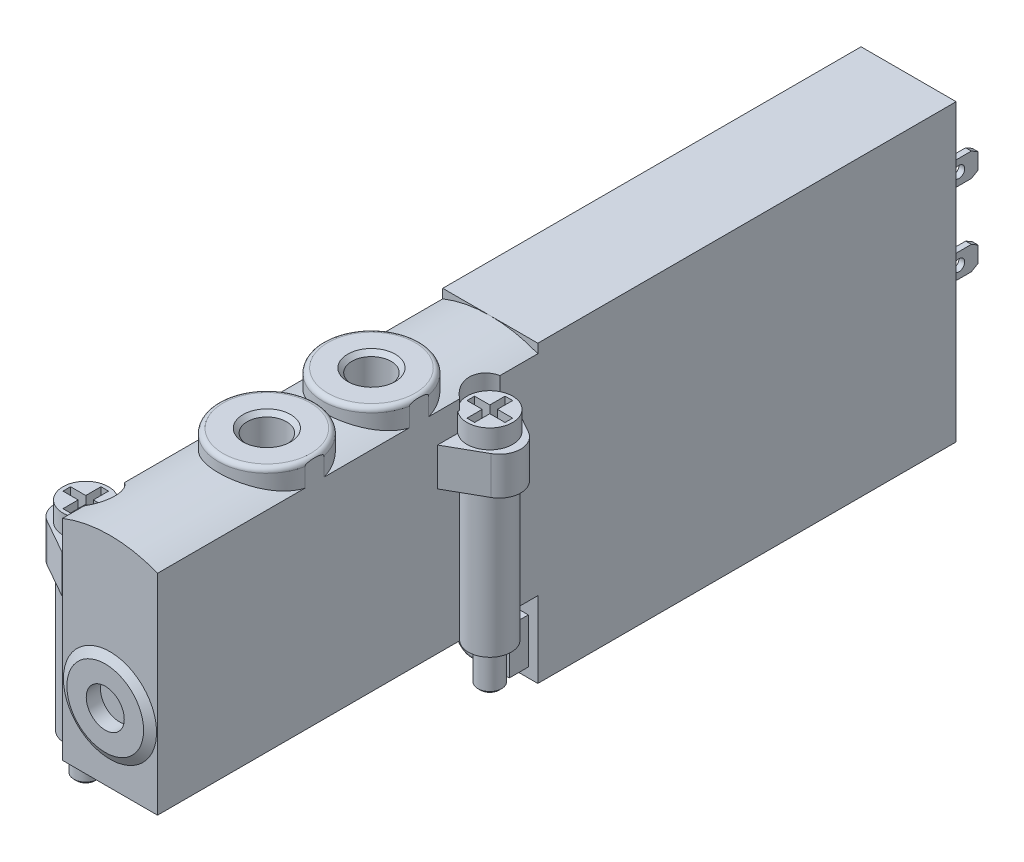
SolidWorks part; units mm, degrees
ref_plane "Front Plane" through (0, 0, 0) normal (0, 0, 1) x (1, 0, 0)
ref_plane "Top Plane" through (0, 0, 0) normal (0, 1, 0) x (1, 0, 0)
ref_plane "Right Plane" through (0, 0, 0) normal (1, 0, 0) x (0, 0, -1)
sketch "Sketch1" plane through (0, 0, 0) normal (1, 0, 0) x (0, 0, -1)
  line L0 (-42, 31) -> (-42, 8)
  line L1 (-42, 8) -> (-2, 8)
  line L2 (-2, 8) -> (-2, 0)
  line L3 (-2, 0) -> (42, 0)
  line L4 (42, 0) -> (42, 31)
  line L5 (42, 31) -> (-42, 31)
extrude "Boss-Extrude1" add sketch "Sketch1" against normal blind 5 and the other way blind 5
sketch "Sketch2" plane through (0, 0, 0) normal (1, 0, 0) x (0, 0, -1)
  line L0 (42, 15.5) -> (42, 17.5)
  line L1 (42, 17.5) -> (44.3, 17.5)
  line L2 (44.3, 17.5) -> (44.5, 17.3)
  line L3 (44.5, 17.3) -> (44.5, 15.5)
  line L4 (44.5, 15.5) -> (42, 15.5)
  line L5 (44.5, 15.5) -> (42, 15.5) construction
revolve "Revolve1" add sketch "Sketch2" angle 360 about L5 reverse direction yes
sketch "Sketch3" plane through (0, 0, 0) normal (1, 0, 0) x (0, 0, -1)
  line L0 (42, 18) -> (42.5, 18.5)
  line L1 (42.5, 18.5) -> (48.3, 18.5)
  line L2 (48.3, 18.5) -> (49, 18.9041)
  line L3 (49, 18.9041) -> (49, 20.5959)
  line L4 (49, 20.5959) -> (48.3, 21)
  line L5 (48.3, 21) -> (42.5, 21)
  line L6 (42.5, 21) -> (42, 21.5)
  line L7 (42, 21.5) -> (42, 18)
  circle A0 centre (47, 19.75) radius 0.6
extrude "Boss-Extrude2" add sketch "Sketch3" against normal blind 0.3 and the other way blind 0.3
sketch "Sketch4" plane through (0, 0, 0) normal (1, 0, 0) x (0, 0, -1)
  line L0 (42, 13) -> (42, 9.5)
  line L1 (42, 9.5) -> (42.5, 10)
  line L2 (42.5, 10) -> (48.3, 10)
  line L3 (48.3, 10) -> (49, 10.4041)
  line L4 (49, 10.4041) -> (49, 12.0959)
  line L5 (49, 12.0959) -> (48.3, 12.5)
  line L6 (48.3, 12.5) -> (42.5, 12.5)
  line L7 (42.5, 12.5) -> (42, 13)
  circle A0 centre (47, 11.25) radius 0.6
extrude "Boss-Extrude3" add sketch "Sketch4" against normal blind 0.3 and the other way blind 0.3
sketch "Sketch5" plane through (0, 0, 0) normal (1, 0, 0) x (0, 0, -1)
  line L0 (-42.5, 15.5) -> (-42.5, 19.534)
  line L1 (-42.5, 19.534) -> (-42, 20.4)
  line L2 (-42, 20.4) -> (-42, 15.5)
  line L3 (-42, 15.5) -> (-42.5, 15.5)
  line L4 (-42, 15.5) -> (-42.5, 15.5) construction
revolve "Revolve2" add sketch "Sketch5" angle 360 about L4 reverse direction yes
ref_plane "Plane1" through (0, 0, 42.5) normal (0, 0, 1) x (1, 0, 0)
sketch "Sketch6" plane through (0, 0, 42.5) normal (0, 0, 1) x (1, 0, 0)
  circle A0 centre (0, 15.5) radius 2
extrude "Cut-Extrude1" cut sketch "Sketch6" along normal blind 1.5 and the other way blind 1.5
ref_plane "Plane2" through (2, 0, 0) normal (1, 0, 0) x (0, 0, -1)
ref_plane "Plane3" through (0, 23, 0) normal (0, 1, 0) x (1, 0, 0)
sketch "Sketch7" plane through (0, 23, 0) normal (0, 1, 0) x (1, 0, 0)
  line L0 (5, -12.55) -> (8.6081, -10.5082)
  line L1 (8.6081, -6.5918) -> (5, -4.55)
  line L2 (5, -4.55) -> (5, -12.55)
  arc A0 (8.6081, -10.5082) -> (8.6081, -6.5918) centre (7.5, -8.55) ccw
extrude "Boss-Extrude4" add sketch "Sketch7" along normal blind 4
sketch "Sketch8" plane through (0, 23, 0) normal (0, 1, 0) x (1, 0, 0)
  line L0 (-8.6081, -40.0082) -> (-5, -42.05)
  line L1 (-5, -42.05) -> (-5, -34.05)
  line L2 (-5, -34.05) -> (-8.6081, -36.0918)
  arc A0 (-8.6081, -36.0918) -> (-8.6081, -40.0082) centre (-7.5, -38.05) ccw
extrude "Boss-Extrude5" add sketch "Sketch8" along normal blind 4
ref_plane "Plane4" through (0, 27, 0) normal (0, 1, 0) x (1, 0, 0)
sketch "Sketch9" plane through (0, 27, 0) normal (0, 1, 0) x (1, 0, 0)
  circle A0 centre (6.5, -8.1) radius 2.6
extrude "Cut-Extrude2" cut sketch "Sketch9" along normal blind 5
sketch "Sketch10" plane through (0, 27, 0) normal (0, 1, 0) x (1, 0, 0)
  circle A0 centre (-6.5, -37.6) radius 2.6
extrude "Cut-Extrude3" cut sketch "Sketch10" along normal blind 5
ref_plane "Plane5" through (6.5, 0, 0) normal (1, 0, 0) x (0, 0, -1)
sketch "Sketch11" plane through (6.5, 0, 0) normal (1, 0, 0) x (0, 0, -1)
  line L0 (-8.55, 29) -> (-6.15, 29)
  line L1 (-6.15, 29) -> (-6.15, 26.5)
  line L2 (-6.15, 26.5) -> (-6.3, 26.5)
  line L3 (-6.3, 26.5) -> (-6.3, 8)
  line L4 (-6.3, 8) -> (-7.3, 8)
  line L5 (-7.3, 8) -> (-7.3, 4.176)
  line L6 (-7.3, 4.176) -> (-7.576, 3.9)
  line L7 (-7.576, 3.9) -> (-8.55, 3.9)
  line L8 (-8.55, 3.9) -> (-8.55, 29)
  line L9 (-8.55, 3.9) -> (-8.55, 29) construction
revolve "Revolve3" add sketch "Sketch11" angle 360 about L9 reverse direction yes
cosmetic thread "Cosmetic Thread1" parameters "D1"=3.5, "D2"=1.948
ref_plane "Plane6" through (-6.5, 0, 0) normal (1, 0, 0) x (0, 0, -1)
sketch "Sketch12" plane through (-6.5, 0, 0) normal (1, 0, 0) x (0, 0, -1)
  line L0 (-38.05, 29) -> (-35.65, 29)
  line L1 (-35.65, 29) -> (-35.65, 26.5)
  line L2 (-35.65, 26.5) -> (-35.8, 26.5)
  line L3 (-35.8, 26.5) -> (-35.8, 8)
  line L4 (-35.8, 8) -> (-36.8, 8)
  line L5 (-36.8, 8) -> (-36.8, 4.176)
  line L6 (-36.8, 4.176) -> (-37.076, 3.9)
  line L7 (-37.076, 3.9) -> (-38.05, 3.9)
  line L8 (-38.05, 3.9) -> (-38.05, 29)
  line L9 (-38.05, 3.9) -> (-38.05, 29) construction
revolve "Revolve4" add sketch "Sketch12" angle 360 about L9 reverse direction yes
cosmetic thread "Cosmetic Thread2" parameters "D1"=3.5, "D2"=1.948
ref_plane "Plane7" through (0, 29, 0) normal (0, 1, 0) x (1, 0, 0)
sketch "Sketch13" plane through (0, 29, 0) normal (0, 1, 0) x (1, 0, 0)
  line L0 (4.5, -8.15) -> (4.5, -8.95)
  line L1 (4.5, -8.95) -> (6.1, -8.95)
  line L2 (6.1, -8.95) -> (6.1, -10.55)
  line L3 (6.1, -10.55) -> (6.9, -10.55)
  line L4 (6.9, -10.55) -> (6.9, -8.95)
  line L5 (6.9, -8.95) -> (8.5, -8.95)
  line L6 (8.5, -8.95) -> (8.5, -8.15)
  line L7 (8.5, -8.15) -> (6.9, -8.15)
  line L8 (6.9, -8.15) -> (6.9, -6.55)
  line L9 (6.9, -6.55) -> (6.1, -6.55)
  line L10 (6.1, -6.55) -> (6.1, -8.15)
  line L11 (6.1, -8.15) -> (4.5, -8.15)
extrude "Cut-Extrude4" cut sketch "Sketch13" against normal blind 1.5
sketch "Sketch14" plane through (0, 29, 0) normal (0, 1, 0) x (1, 0, 0)
  line L0 (-8.5, -37.65) -> (-8.5, -38.45)
  line L1 (-8.5, -38.45) -> (-6.9, -38.45)
  line L2 (-6.9, -38.45) -> (-6.9, -40.05)
  line L3 (-6.9, -40.05) -> (-6.1, -40.05)
  line L4 (-6.1, -40.05) -> (-6.1, -38.45)
  line L5 (-6.1, -38.45) -> (-4.5, -38.45)
  line L6 (-4.5, -38.45) -> (-4.5, -37.65)
  line L7 (-4.5, -37.65) -> (-6.1, -37.65)
  line L8 (-6.1, -37.65) -> (-6.1, -36.05)
  line L9 (-6.1, -36.05) -> (-6.9, -36.05)
  line L10 (-6.9, -36.05) -> (-6.9, -37.65)
  line L11 (-6.9, -37.65) -> (-8.5, -37.65)
extrude "Cut-Extrude5" cut sketch "Sketch14" against normal blind 1.5
ref_plane "Plane8" through (0, 0, 4) normal (0, 0, 1) x (1, 0, 0)
sketch "Sketch15" plane through (0, 0, 4) normal (0, 0, 1) x (1, 0, 0)
  line L0 (-4, 1) -> (-3.5, 1)
  line L1 (3.5, 1) -> (4, 1)
  line L2 (4, 1) -> (4, 5.75)
  line L3 (4, 5.75) -> (2.5, 5.75)
  line L4 (2.5, 5.75) -> (2.5, 7.95)
  line L5 (2.5, 7.95) -> (-2.5, 7.95)
  line L6 (-2.5, 7.95) -> (-2.5, 5.75)
  line L7 (-2.5, 5.75) -> (-4, 5.75)
  line L8 (-4, 5.75) -> (-4, 1)
  arc A0 (-3.5, 1) -> (-2, 2.5) centre (-3.5, 2.5) ccw
  arc A1 (-2, 2.5) -> (2, 2.5) centre (0, 2.5) cw
  arc A2 (2, 2.5) -> (3.5, 1) centre (3.5, 2.5) ccw
extrude "Boss-Extrude6" add sketch "Sketch15" against normal blind 2
sketch "Sketch16" plane through (0, 0, 0) normal (1, 0, 0) x (0, 0, -1)
  line L0 (-4, 2.5) -> (-4, 4)
  line L1 (-3.7, 4.3) -> (-2, 4.3)
  line L2 (-2, 4.3) -> (-2, 2.5)
  line L3 (-2, 2.5) -> (-4, 2.5)
  line L4 (-2, 2.5) -> (-4, 2.5) construction
  arc A0 (-4, 4) -> (-3.7, 4.3) centre (-3.7, 4) cw
revolve "Revolve5" add sketch "Sketch16" angle 360 about L4 reverse direction yes
ref_plane "Plane9" through (0, 0, 4) normal (0, 0, 1) x (1, 0, 0)
sketch "Sketch17" plane through (0, 0, 4) normal (0, 0, 1) x (1, 0, 0)
  line L0 (-0.75, 2.933) -> (-0.75, 2.067)
  line L1 (-0.75, 2.067) -> (0, 1.634)
  line L2 (0, 1.634) -> (0.75, 2.067)
  line L3 (0.75, 2.067) -> (0.75, 2.933)
  line L4 (0.75, 2.933) -> (0, 3.366)
  line L5 (0, 3.366) -> (-0.75, 2.933)
extrude "Cut-Extrude6" cut sketch "Sketch17" along normal blind 1.2 and the other way blind 1.2
sketch "Sketch18" plane through (0, 0, 0) normal (1, 0, 0) x (0, 0, -1)
  line L0 (-8.1, 8) -> (-10.75, 8)
  line L1 (-10.75, 8) -> (-10.6, 8.15)
  line L2 (-10.6, 8.15) -> (-10.6, 11)
  line L3 (-10.6, 11) -> (-8.1, 11)
  line L4 (-8.1, 11) -> (-8.1, 8)
  line L5 (-8.1, 11) -> (-8.1, 8) construction
revolve "Cut-Revolve1" cut sketch "Sketch18" angle 360 about L5 reverse direction yes
sketch "Sketch19" plane through (0, 0, 0) normal (1, 0, 0) x (0, 0, -1)
  line L0 (-14.1, 8) -> (-16.75, 8)
  line L1 (-16.75, 8) -> (-16.6, 8.15)
  line L2 (-16.6, 8.15) -> (-16.6, 11)
  line L3 (-16.6, 11) -> (-14.1, 11)
  line L4 (-14.1, 11) -> (-14.1, 8)
  line L5 (-14.1, 11) -> (-14.1, 8) construction
revolve "Cut-Revolve2" cut sketch "Sketch19" angle 360 about L5 reverse direction yes
sketch "Sketch20" plane through (0, 0, 0) normal (1, 0, 0) x (0, 0, -1)
  line L0 (-19.6, 8) -> (-22.25, 8)
  line L1 (-22.25, 8) -> (-22.1, 8.15)
  line L2 (-22.1, 8.15) -> (-22.1, 11)
  line L3 (-22.1, 11) -> (-19.6, 11)
  line L4 (-19.6, 11) -> (-19.6, 8)
  line L5 (-19.6, 11) -> (-19.6, 8) construction
revolve "Cut-Revolve3" cut sketch "Sketch20" angle 360 about L5 reverse direction yes
sketch "Sketch21" plane through (0, 0, 0) normal (1, 0, 0) x (0, 0, -1)
  line L0 (-25.1, 8) -> (-27.75, 8)
  line L1 (-27.75, 8) -> (-27.6, 8.15)
  line L2 (-27.6, 8.15) -> (-27.6, 11)
  line L3 (-27.6, 11) -> (-25.1, 11)
  line L4 (-25.1, 11) -> (-25.1, 8)
  line L5 (-25.1, 11) -> (-25.1, 8) construction
revolve "Cut-Revolve4" cut sketch "Sketch21" angle 360 about L5 reverse direction yes
sketch "Sketch22" plane through (0, 0, 0) normal (1, 0, 0) x (0, 0, -1)
  line L0 (-31.1, 8) -> (-33.75, 8)
  line L1 (-33.75, 8) -> (-33.6, 8.15)
  line L2 (-33.6, 8.15) -> (-33.6, 11)
  line L3 (-33.6, 11) -> (-31.1, 11)
  line L4 (-31.1, 11) -> (-31.1, 8)
  line L5 (-31.1, 11) -> (-31.1, 8) construction
revolve "Cut-Revolve5" cut sketch "Sketch22" angle 360 about L5 reverse direction yes
ref_plane "Plane10" through (0, 0, 42) normal (0, 0, 1) x (1, 0, 0)
sketch "Sketch23" plane through (0, 0, 42) normal (0, 0, 1) x (1, 0, 0)
  line L0 (-5.1, 37.7962) -> (-5.1, 30)
  line L1 (5.1, 30) -> (5.1, 37.7962)
  line L2 (5.1, 37.7962) -> (-5.1, 37.7962)
  arc A0 (-5.1, 30) -> (5.1, 30) centre (0, 17.495) cw
extrude "Cut-Extrude7" cut sketch "Sketch23" along normal blind 40 and the other way blind 40
sketch "Sketch24" plane through (0, 0, 0) normal (1, 0, 0) x (0, 0, -1)
  line L0 (-25.5, 32.5) -> (-20.9, 32.5)
  line L1 (-20.4, 32) -> (-20.4, 29.5)
  line L2 (-20.4, 29.5) -> (-25.5, 29.5)
  line L3 (-25.5, 29.5) -> (-25.5, 32.5)
  line L4 (-25.5, 29.5) -> (-25.5, 32.5) construction
  arc A0 (-20.9, 32.5) -> (-20.4, 32) centre (-20.9, 32) cw
revolve "Revolve6" add sketch "Sketch24" angle 360 about L4 reverse direction yes
sketch "Sketch25" plane through (0, 0, 0) normal (1, 0, 0) x (0, 0, -1)
  line L0 (-14.5, 32.5) -> (-9.9, 32.5)
  line L1 (-9.4, 32) -> (-9.4, 29.5)
  line L2 (-9.4, 29.5) -> (-14.5, 29.5)
  line L3 (-14.5, 29.5) -> (-14.5, 32.5)
  line L4 (-14.5, 29.5) -> (-14.5, 32.5) construction
  arc A0 (-9.9, 32.5) -> (-9.4, 32) centre (-9.9, 32) cw
revolve "Revolve7" add sketch "Sketch25" angle 360 about L4 reverse direction yes
ref_plane "Plane11" through (0, 0, 20) normal (0, 0, 1) x (1, 0, 0)
sketch "Sketch26" plane through (0, 0, 20) normal (0, 0, 1) x (1, 0, 0)
  line L0 (-8, 29.5) -> (-5, 29.5)
  line L1 (-5, 29.5) -> (-5, 32.5)
  line L2 (-5, 32.5) -> (5, 32.5)
  line L3 (5, 32.5) -> (5, 29.5)
  line L4 (5, 29.5) -> (8, 29.5)
  line L5 (8, 29.5) -> (8, 35.5)
  line L6 (8, 35.5) -> (-8, 35.5)
  line L7 (-8, 35.5) -> (-8, 29.5)
extrude "Cut-Extrude8" cut sketch "Sketch26" along normal blind 15 and the other way blind 15
sketch "Sketch27" plane through (0, 0, 0) normal (1, 0, 0) x (0, 0, -1)
  line L0 (-25.5, 32.5) -> (-23, 32.5)
  line L1 (-23, 32.5) -> (-23.433, 32.067)
  line L2 (-23.433, 32.067) -> (-23.433, 27.5)
  line L3 (-23.433, 27.5) -> (-25.5, 27.5)
  line L4 (-25.5, 27.5) -> (-25.5, 32.5)
  line L5 (-25.5, 27.5) -> (-25.5, 32.5) construction
revolve "Cut-Revolve6" cut sketch "Sketch27" angle 360 about L5 reverse direction yes
cosmetic thread "Cosmetic Thread3" parameters "D1"=5, "D2"=5
sketch "Sketch28" plane through (0, 0, 0) normal (1, 0, 0) x (0, 0, -1)
  line L0 (-14.5, 32.5) -> (-12, 32.5)
  line L1 (-12, 32.5) -> (-12.433, 32.067)
  line L2 (-12.433, 32.067) -> (-12.433, 27.5)
  line L3 (-12.433, 27.5) -> (-14.5, 27.5)
  line L4 (-14.5, 27.5) -> (-14.5, 32.5)
  line L5 (-14.5, 27.5) -> (-14.5, 32.5) construction
revolve "Cut-Revolve7" cut sketch "Sketch28" angle 360 about L5 reverse direction yes
cosmetic thread "Cosmetic Thread4" parameters "D1"=5, "D2"=5
